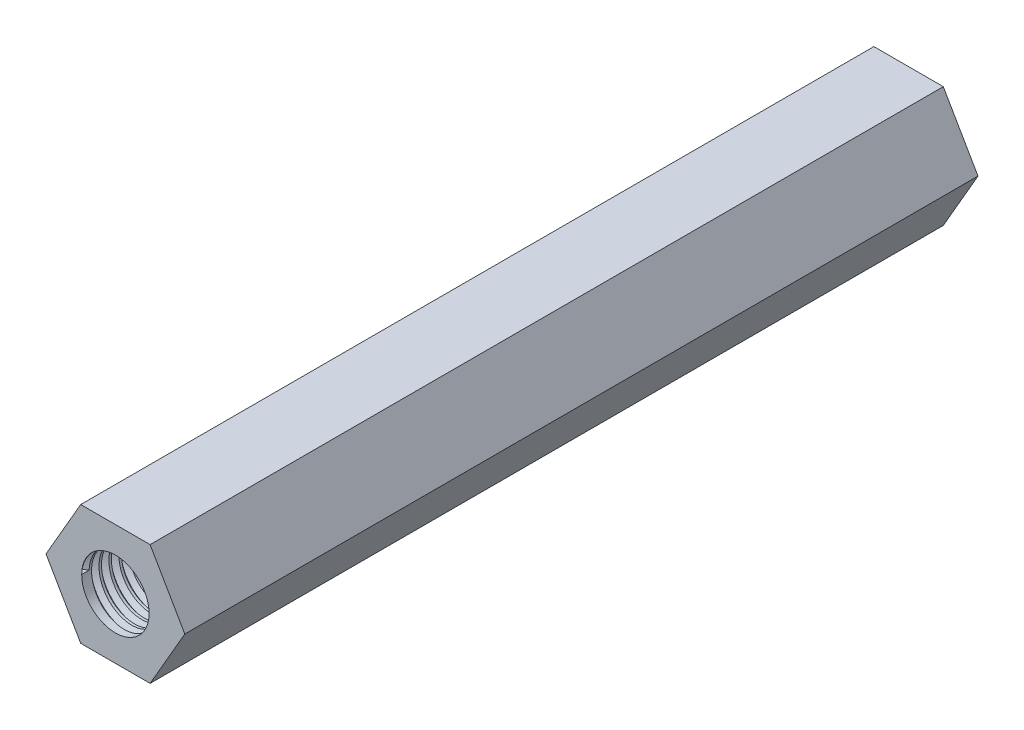
SolidWorks part; units mm, degrees
material "1.7036 (28CrS4)"
ref_plane "Plan de face" through (0, 0, 0) normal (0, 0, 1) x (1, 0, 0)
ref_plane "Plan de dessus" through (0, 0, 0) normal (0, 1, 0) x (1, 0, 0)
ref_plane "Plan de droite" through (0, 0, 0) normal (1, 0, 0) x (0, 0, -1)
sketch "Esquisse1" plane through (0, 0, 0) normal (0, 0, 1) x (1, 0, 0)
  line L0 (0, 3.5) -> (7, 3.5) construction
  line L1 (0, 0) -> (7, 0) construction
  line L2 (0, 0) -> (0, 7) construction
  line L3 (0, 7) -> (7, 7) construction
  line L4 (7, 0) -> (7, 7) construction
  line L5 (3.5, 7) -> (3.5, 0) construction
  line L7 (5.25, 0.4689) -> (7, 3.5)
  line L8 (7, 3.5) -> (5.25, 6.5311)
  line L9 (5.25, 6.5311) -> (1.75, 6.5311)
  line L10 (1.75, 6.5311) -> (0, 3.5)
  line L11 (0, 3.5) -> (1.75, 0.4689)
  line L12 (1.75, 0.4689) -> (5.25, 0.4689)
  circle A0 centre (3.5, 3.5) radius 3.5 construction
  dimension "D3" = 7
  dimension "D1" = 7
  dimension "D2" = 7
extrude "Boss.-Extru.1" add sketch "Esquisse1" along normal blind 40
sketch "Esquisse2" plane through (0, 0, 40) normal (0, 0, 1) x (1, 0, 0)
  line L0 (3.5, 6.5311) -> (3.5, 0.4689) construction
  line L1 (0.875, 1.9845) -> (6.125, 5.0155) construction
  line L6 (1.75, 0.4689) -> (5.25, 0.4689)
  line L7 (5.25, 0.4689) -> (7, 3.5)
  line L8 (7, 3.5) -> (5.25, 6.5311)
  line L9 (5.25, 6.5311) -> (1.75, 6.5311)
  line L10 (1.75, 6.5311) -> (0, 3.5)
  line L11 (0, 3.5) -> (1.75, 0.4689)
  line L12 (1.75, 0.4689) -> (5.25, 0.4689)
  line L13 (5.25, 0.4689) -> (7, 3.5)
  line L14 (7, 3.5) -> (5.25, 6.5311)
  line L15 (5.25, 6.5311) -> (1.75, 6.5311)
  line L16 (1.75, 6.5311) -> (0, 3.5)
  line L17 (0, 3.5) -> (1.75, 0.4689)
  circle A0 centre (3.5, 3.5) radius 1.5
  dimension "D2" = 3
  dimension "D1" = 0
hole_wizard "Dégagement M31" positions "Esquisse6" profile "Esquisse7" hole size "M3" standard "ISO"
sketch "Esquisse6" plane through (0, 0, 40) normal (0, 0, 1) x (1, 0, 0)
  point P0 (3.5, 3.5)
sketch "Esquisse7" plane through (3.5, 3.5, 40) normal (1, 0, 0) x (0, -1, 0)
  line L0 (0, 0) -> (0, 16.0215)
  line L1 (0, 16.0215) -> (1.7, 15)
  line L2 (1.7, 15) -> (1.7, 0)
  line L5 (1.7, 0) -> (0, 0)
  line L10 (0, 16.0215) -> (-1.7, 15) construction
  line L11 (0, -6.35) -> (0, 107.95) construction
  dimension "Diamètre du perçage" = 3.4
  dimension "Profondeur du perçage" = 15
  dimension "Angle de pointe" = 118
thread "Filetage1" pitch 0.5 start angle 0, offset 0, length 15, pitch 0.5, diameter 3.4
ref_plane "Plan1" through (1.8, 3.5, 40) normal (0, -1, 0) x (-1, 0, 0)
sketch "Profil de filetage1" plane through (1.8, 3.5, 40) normal (0, -1, 0) x (-1, 0, 0)
  line L0 (0, 0) -> (0, 0.5) construction
  line L1 (0, 0) -> (0.2706, 0.1562)
  line L2 (0.2706, 0.1562) -> (0.2706, 0.2187)
  line L3 (0.2706, 0.2187) -> (0, 0.375)
  line L4 (0.2706, 0.1875) -> (0, 0.1875) construction
  line L11 (0, 0) -> (0, 0.375)
  point P2 (0, 0)
  dimension "Pitch" = 0.5
  dimension "Profile_Angle" = 60
  dimension "Profile_Land" = 0.0625
  dimension "Profile_Height" = 0.2706
hole_wizard "Dégagement M32" positions "Esquisse10" profile "Esquisse11" hole size "M3" standard "ISO"
sketch "Esquisse10" plane through (0, 0, 0) normal (0, 0, -1) x (-1, 0, 0)
  point P0 (-3.5, 3.5)
sketch "Esquisse11" plane through (3.5, 3.5, 0) normal (1, 0, 0) x (0, 1, 0)
  line L0 (0, 0) -> (0, 9.0215)
  line L1 (0, 9.0215) -> (1.7, 8)
  line L2 (1.7, 8) -> (1.7, 0)
  line L5 (1.7, 0) -> (0, 0)
  line L10 (0, 9.0215) -> (-1.7, 8) construction
  line L11 (0, -6.35) -> (0, 107.95) construction
  dimension "Diamètre du perçage" = 3.4
  dimension "Profondeur du perçage" = 8
  dimension "Angle de pointe" = 118
sketch "Esquisse12" plane through (0, 0, 0) normal (0, 0, -1) x (-1, 0, 0)
  line L6 (-5.25, 0.4689) -> (-1.75, 0.4689)
  line L7 (-1.75, 0.4689) -> (0, 3.5)
  line L8 (0, 3.5) -> (-1.75, 6.5311)
  line L9 (-1.75, 6.5311) -> (-5.25, 6.5311)
  line L10 (-5.25, 6.5311) -> (-7, 3.5)
  line L11 (-7, 3.5) -> (-5.25, 0.4689)
  line L12 (-5.25, 0.4689) -> (-1.75, 0.4689)
  line L13 (-1.75, 0.4689) -> (0, 3.5)
  line L14 (0, 3.5) -> (-1.75, 6.5311)
  line L15 (-1.75, 6.5311) -> (-5.25, 6.5311)
  line L16 (-5.25, 6.5311) -> (-7, 3.5)
  line L17 (-7, 3.5) -> (-5.25, 0.4689)
  circle A0 centre (-3.5, 3.5) radius 1.5
  dimension "D2" = 3
  dimension "D1" = 0
extrude "Enlèv. mat.-Extru.1" [suppressed] cut sketch "Esquisse12" against normal blind 15
thread "Filetage2" pitch 0.5 profile "Profil de filetage2" start angle 0, offset 0, length 10, pitch 0.5, diameter 3.4
ref_plane "Plan2" through (5.2, 3.5, 0) normal (0, -1, 0) x (1, 0, 0)
sketch "Profil de filetage2" plane through (5.2, 3.5, 0) normal (0, -1, 0) x (1, 0, 0)
  line L0 (0, 0) -> (0, 0.5) construction
  line L1 (0, 0) -> (0.2706, 0.1562)
  line L2 (0.2706, 0.1562) -> (0.2706, 0.2187)
  line L3 (0.2706, 0.2187) -> (0, 0.375)
  line L4 (0.2706, 0.1875) -> (0, 0.1875) construction
  line L11 (0, 0) -> (0, 0.375)
  point P2 (0, 0)
  dimension "Pitch" = 0.5
  dimension "Profile_Angle" = 60
  dimension "Profile_Land" = 0.0625
  dimension "Profile_Height" = 0.2706
equation "\"diam_cercle_circons\"= 7"
equation "\"D1@Esquisse1\"=\"diam_cercle_circons\""
equation "\"D2@Esquisse1\"=\"diam_cercle_circons\""
equation "\"Hauteur\"= 40"
equation "\"D1@Boss.-Extru.1\"=\"Hauteur\""
equation "\"D3@Esquisse1\"=\"diam_cercle_circons\""
